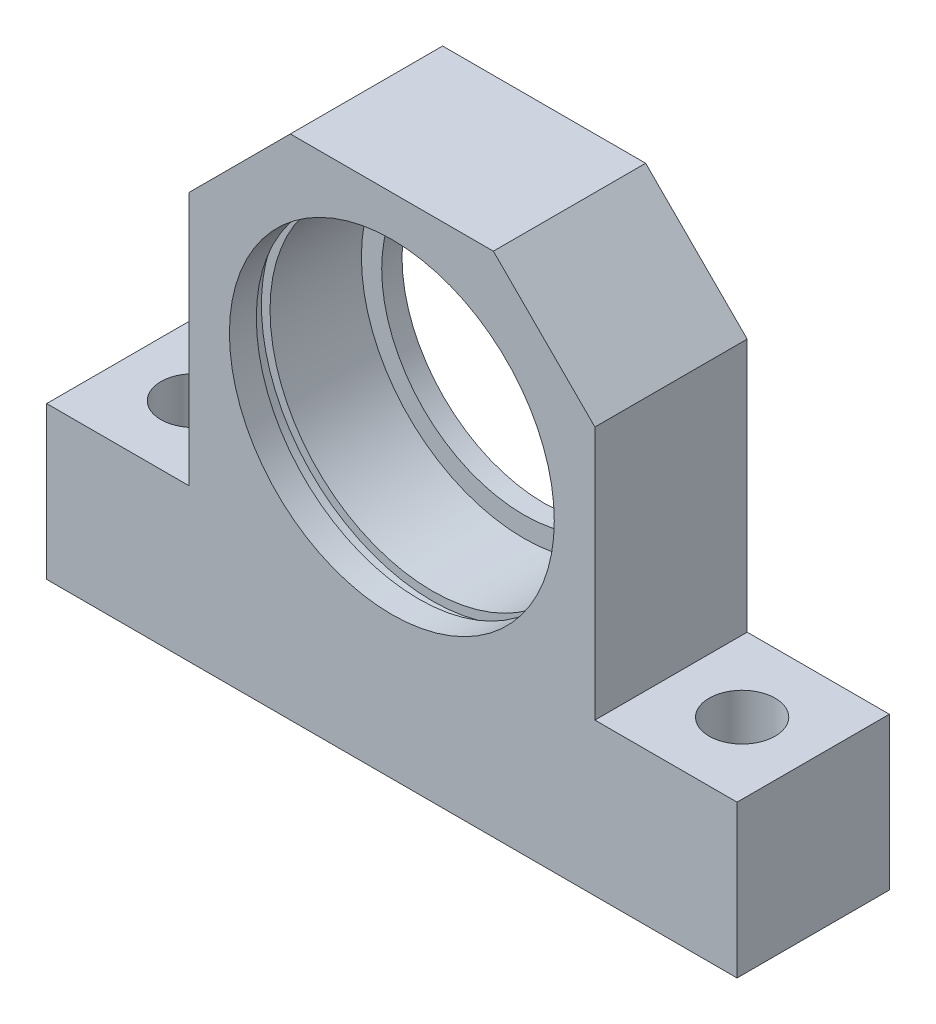
SolidWorks part; units mm, degrees
ref_plane "Front Plane" through (0, 0, 0) normal (0, 0, 1) x (1, 0, 0)
ref_plane "Top Plane" through (0, 0, 0) normal (0, 1, 0) x (1, 0, 0)
ref_plane "Right Plane" through (0, 0, 0) normal (1, 0, 0) x (0, 0, -1)
sketch "Sketch1" plane through (0, 0, 0) normal (0, 0, 1) x (1, 0, 0)
  line L0 (-20, 50) -> (20, 50)
  line L1 (20, 50) -> (20, 15)
  line L2 (20, 15) -> (34, 15)
  line L3 (34, 15) -> (34, 0)
  line L4 (34, 0) -> (-34, 0)
  line L5 (-34, 0) -> (-34, 15)
  line L6 (-34, 15) -> (-20, 15)
  line L7 (-20, 15) -> (-20, 50)
  line L8 (0, 50) -> (0, 0) construction
  point P12 (0, 30)
  dimension "L" = 68
  dimension "S" = 15
  dimension "L2" = 40
  dimension "H_s" = 30
  dimension "H" = 50
  dimension "MSM_6" = 20
extrude "Boss-Extrude1" add sketch "Sketch1" against normal blind 15
sketch "Sketch2" plane through (0, 0, 0) normal (1, 0, 0) x (0, 0, -1)
  line L0 (15, 30) -> (0, 30) construction
  line L1 (2.65, 46) -> (2.65, 46.85)
  line L2 (13, 46) -> (4, 46)
  line L3 (13, 46) -> (13, 44)
  line L4 (13, 44) -> (15, 44)
  line L5 (2.65, 46.85) -> (4, 46.85)
  line L6 (4, 46.85) -> (4, 46)
  line L7 (0, 46) -> (0, 30)
  line L8 (0, 30) -> (15, 30)
  line L9 (15, 30) -> (15, 44)
  line L11 (0, 15) -> (0, 50) construction
  line L12 (2.65, 46) -> (0, 46)
  line L13 (0, 15) -> (0, 50) construction
  line L14 (15, 15) -> (15, 50) construction
  dimension "D" = 32
  dimension "DH_s" = 28
  dimension "B" = 9
  dimension "H_s" = 30
  dimension "L1_s" = 2
  dimension "MSM_2" = 1.35
  dimension "MSM_1" = 33.7
revolve "Cut-Revolve1" cut sketch "Sketch2" angle 360 about L0
hole_wizard "Diameter Hole1" positions "Sketch4" profile "Sketch3" hole size "Ø5.5" standard "JIS" end condition through all
sketch "Sketch4" plane through (0, 15, 0) normal (0, 1, 0) x (1, 0, 0)
  line L10 (0, 0) -> (0, 15) construction
  line L11 (20, 15) -> (-20, 15) construction
  line L12 (-34, 7.5) -> (34, 7.5) construction
  line L13 (-34, 15) -> (-34, 0) construction
  line L14 (34, 15) -> (34, 0) construction
  point P0 (-27, 7.5)
  point P6 (27, 7.5)
  dimension "L1" = 54
  dimension "T/2" = 7.5
sketch "Sketch3" plane through (-27, 15, -7.5) normal (1, 0, 0) x (0, 0, 1)
  line L0 (0, 0) -> (0, 15)
  line L1 (0, 15) -> (3.25, 15)
  line L2 (3.25, 15) -> (3.25, 0)
  line L5 (3.25, 0) -> (0, 0)
  line L11 (0, 0) -> (0, 15) construction
  dimension "D1_s" = 6.5
  dimension "Thru Hole Depth" = 15
chamfer "Chamfer1" distance 10 angle 45 2 edges at (-20, 50, -7.5) (20, 50, -7.5)
chamfer "Chamfer2" [suppressed] distance 2 angle 45
